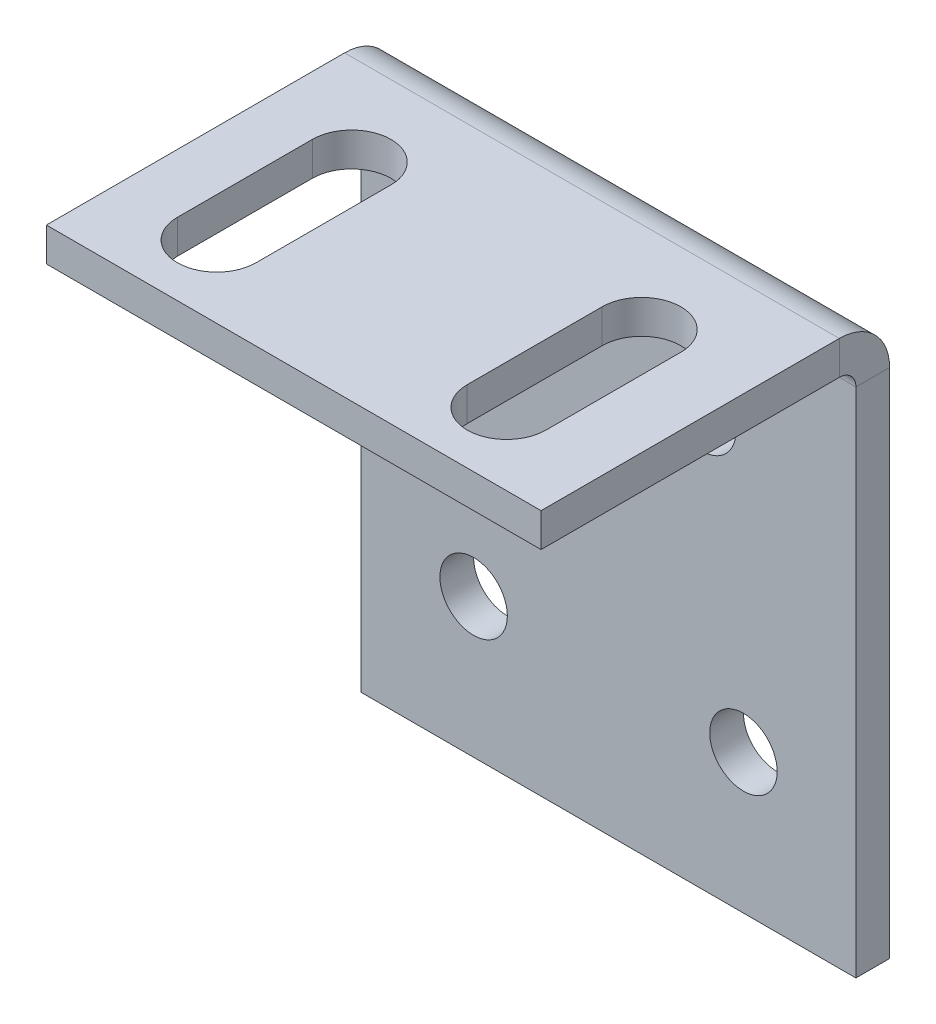
SolidWorks part; units mm, degrees
note: The reader was unsure of these and kept them because the rebuilt part matched: flange length of "Edge-Flange1".
ref_plane "Front Plane" through (0, 0, 0) normal (0, 0, 1) x (1, 0, 0)
ref_plane "Top Plane" through (0, 0, 0) normal (0, 1, 0) x (1, 0, 0)
ref_plane "Right Plane" through (0, 0, 0) normal (1, 0, 0) x (0, 0, -1)
sketch "Sketch1" plane through (0, 0, 0) normal (0, 0, 1) x (1, 0, 0)
  line L1 (-10.1655, 4.969) -> (11.8345, 4.969)
  line L2 (-10.1655, 4.969) -> (-10.1655, -20.031)
  line L3 (-10.1655, -20.031) -> (11.8345, -20.031)
  line L4 (11.8345, 4.969) -> (11.8345, -20.031)
  circle A0 centre (6.8345, -13.8348) radius 1.5
  circle A1 centre (-5.1655, -13.8348) radius 1.5
  circle A2 centre (-3.4155, -1.6628) radius 1.5
  circle A3 centre (4.9945, -1.6628) radius 1.5
  dimension "D3" = 3
  dimension "D4" = 15.25
  dimension "D5" = 6.84
  dimension "D6" = 5
  dimension "D7" = 12
  dimension "D1" = 22
  dimension "D2" = 25
base flange "Base-Flange1" sketch "Sketch1" thickness 1.5 reverse thickness direction no parameters "D1"=0.7366
edge flange "Edge-Flange1" sketch "Sketch10" flange angle 90 flange length 15.5 flange position material inside bend radius 0.7366 thickness 1.5 relief rectangular parameters "D6"=10
sketch "Sketch10" plane through (0, 4.969, 0) normal (0, 1, 0) x (-1, 0, 0)
  line L0 (-11.8345, 0) -> (10.1655, 0) construction
  line L1 (-11.8345, 0) -> (10.1655, 0)
  line L2 (-11.8345, 0) -> (-11.8345, 14)
  line L3 (-11.8345, 14) -> (10.1655, 14)
  line L4 (10.1655, 14) -> (10.1655, 0)
bend "EdgeBend1" bend radius 0.7366 bend angle 90 parameters "D5"=1
sketch "Sketch11" plane through (0, 4.969, 0) normal (0, 1, 0) x (1, 0, 0)
  line L0 (-4.0507, -10.7895) -> (-4.0507, -4.7895)
  line L1 (-7.5507, -10.7895) -> (-7.5507, -4.7895)
  line L2 (8.8405, -10.7895) -> (8.8405, -4.7895)
  line L3 (5.3405, -10.7895) -> (5.3405, -4.7895)
  arc A0 (5.3405, -10.7895) -> (8.8405, -10.7895) centre (7.0905, -10.7895) ccw
  arc A1 (8.8405, -4.7895) -> (5.3405, -4.7895) centre (7.0905, -4.7895) ccw
  arc A2 (-4.0507, -4.7895) -> (-7.5507, -4.7895) centre (-5.8007, -4.7895) ccw
  arc A3 (-7.5507, -10.7895) -> (-4.0507, -10.7895) centre (-5.8007, -10.7895) ccw
  dimension "D2" = 3.5
  dimension "D3" = 6
  dimension "D1" = 6
extrude "Cut-Extrude1" cut sketch "Sketch11" against normal blind 10 normal cut yes
sketch "Bend-Lines1" [suppressed] plane through (0, 0, 0) normal (0, 1, 0) x (1, 0, 0)
sketch "Bounding-Box1" [suppressed] plane through (0, 0, 0) normal (0, 1, 0) x (1, 0, 0)
sheet metal parameters "Sheet-Metal1" thickness 1.5 parameters "D1"=0.7366
flat pattern "Flat-Pattern1" [suppressed]
sketch "Bend-Lines2" plane through (0, 0, 0) normal (0, 1, 0) x (1, 0, 0)
sketch3d "Bounding-Box2" [suppressed]
  line L0 (11.8345, 4.969, 0) -> (11.8345, -20.031, 0) construction
  line L1 (-10.1655, 4.969, 0) -> (-10.1655, -20.031, 0) construction
  line L2 (11.8345, 4.969, 0) -> (-10.1655, 4.969, 0) construction
  line L3 (11.8345, -20.031, 0) -> (-10.1655, -20.031, 0) construction
sheet metal parameters "Sheet-Metal2" thickness 1.5 parameters "D1"=0.7366
flat pattern "Flat-Pattern1"
sketch "Bend-Lines2" plane through (0, 0, 0) normal (0, 0, 1) x (1, 0, 0)
  line L0 (11.8345, 3.8999) -> (-10.1655, 3.8999) construction
  line L1 (11.8345, 3.8999) -> (-10.1655, 3.8999) construction
sketch3d "Bounding-Box2" [suppressed]
  line L0 (11.8345, 18.3309, 0) -> (11.8345, -20.031, 0) construction
  line L1 (-10.1655, 18.3309, 0) -> (-10.1655, -20.031, 0) construction
  line L2 (11.8345, 18.3309, 0) -> (-10.1655, 18.3309, 0) construction
  line L3 (11.8345, -20.031, 0) -> (-10.1655, -20.031, 0) construction
bend of the flat pattern "Flatten-<EdgeBend1>1"
sheet metal parameters "Sheet-Metal3" thickness 1.5 parameters "D1"=0.7366
flat pattern "Flat-Pattern1"
sketch "Bend-Lines2" plane through (0, 0, 0) normal (0, 0, 1) x (1, 0, 0)
  line L0 (11.8345, 3.8999) -> (-10.1655, 3.8999) construction
  line L1 (11.8345, 3.8999) -> (-10.1655, 3.8999) construction
sketch3d "Bounding-Box2" [suppressed]
  line L0 (11.8345, 18.3309, 0) -> (11.8345, -20.031, 0) construction
  line L1 (-10.1655, 18.3309, 0) -> (-10.1655, -20.031, 0) construction
  line L2 (11.8345, 18.3309, 0) -> (-10.1655, 18.3309, 0) construction
  line L3 (11.8345, -20.031, 0) -> (-10.1655, -20.031, 0) construction
bend of the flat pattern "Flatten-<EdgeBend1>1"
